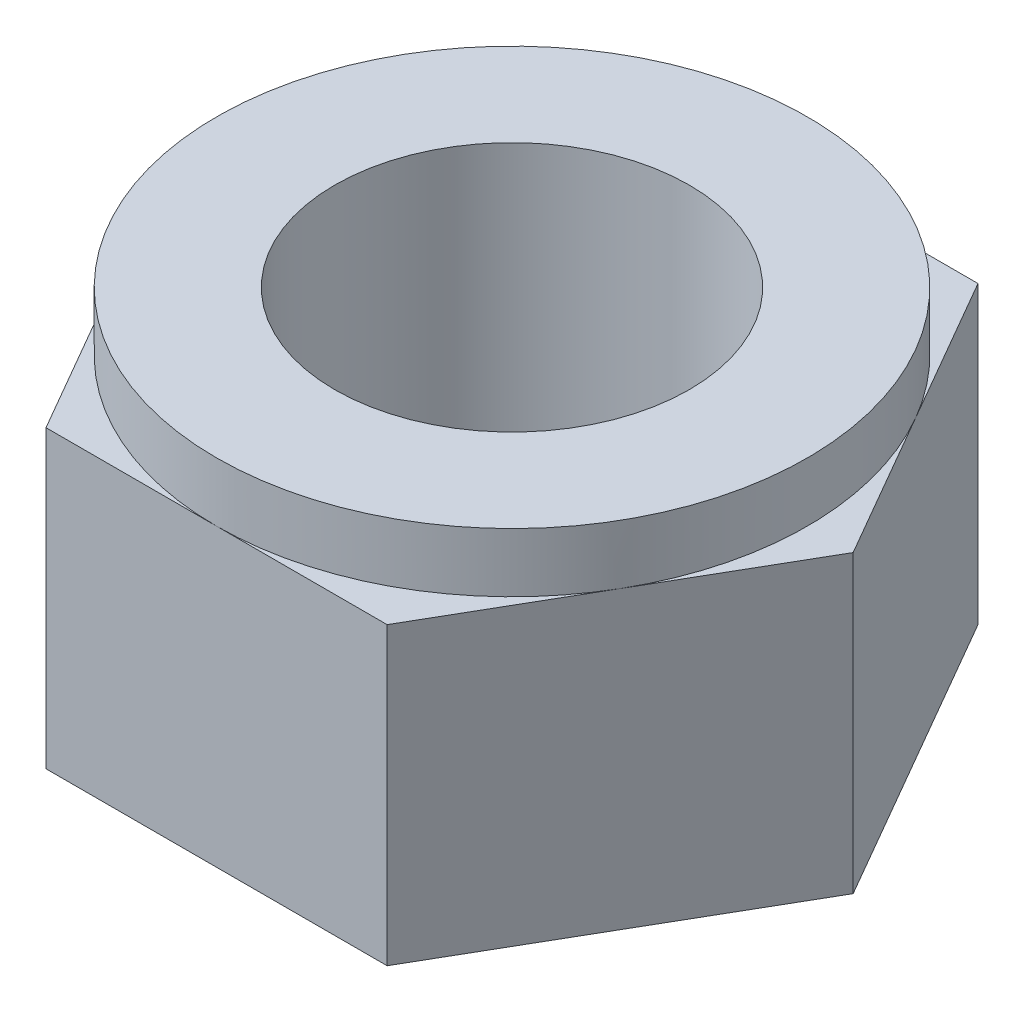
SolidWorks part; units mm, degrees
ref_plane "前视基准面" through (0, 0, 0) normal (0, 0, 1) x (1, 0, 0)
ref_plane "上视基准面" through (0, 0, 0) normal (0, 1, 0) x (1, 0, 0)
ref_plane "右视基准面" through (0, 0, 0) normal (1, 0, 0) x (0, 0, -1)
other "Configuration Table"
sketch "草图1" plane through (0, 0, 0) normal (0, 1, 0) x (1, 0, 0)
  line L1 (5.7735, 0) -> (2.8868, 5)
  line L2 (2.8868, 5) -> (-2.8868, 5)
  line L3 (-2.8868, 5) -> (-5.7735, 0)
  line L4 (-5.7735, 0) -> (-2.8868, -5)
  line L5 (-2.8868, -5) -> (2.8868, -5)
  line L6 (2.8868, -5) -> (5.7735, 0)
  circle A0 centre (0, 0) radius 5 construction
  dimension "D1" = 10
extrude "凸台-拉伸1" add sketch "草图1" along normal blind 5
sketch "草图2" plane through (0, 5, 0) normal (0, 1, 0) x (1, 0, 0)
  line L0 (2.8868, -5) -> (5.7735, 0) construction
  circle A0 centre (0, 0) radius 5
extrude "凸台-拉伸2" add sketch "草图2" along normal blind 1
sketch "草图3" plane through (0, 0, 0) normal (0, -1, 0) x (1, 0, 0)
  circle A0 centre (0, 0) radius 3
  dimension "D1" = 6
extrude "切除-拉伸1" cut sketch "草图3" against normal through all
ref_axis "基准轴1" through (0, 9.2881, 0) along (0, -1, 0)
